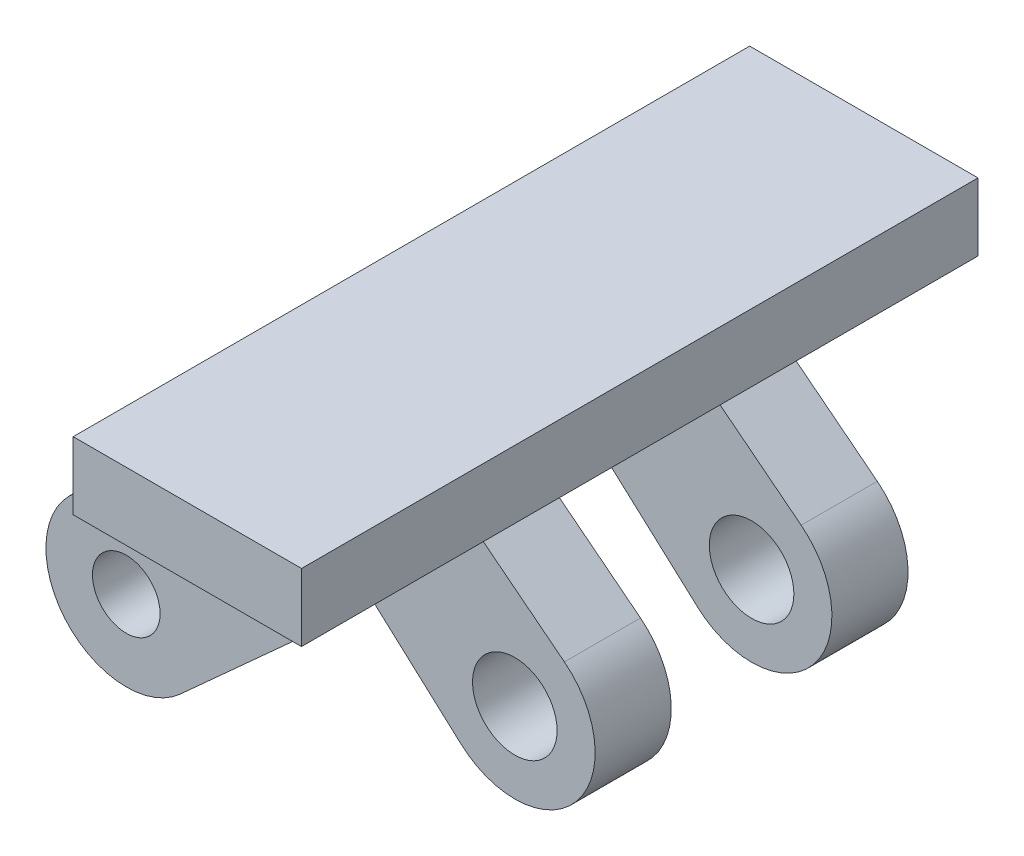
SolidWorks part; units mm, degrees
ref_plane "前视基准面" through (0, 0, 0) normal (0, 0, 1) x (1, 0, 0)
ref_plane "上视基准面" through (0, 0, 0) normal (0, 1, 0) x (1, 0, 0)
ref_plane "右视基准面" through (0, 0, 0) normal (1, 0, 0) x (0, 0, -1)
sketch "草图1" plane through (0, 0, 0) normal (0, 0, 1) x (1, 0, 0)
  line L1 (0, 0) -> (5.4, 0)
  line L2 (0, 0) -> (0, -1.6)
  line L3 (0, -1.6) -> (5.4, -1.6)
  line L4 (5.4, 0) -> (5.4, -1.6)
  dimension "D1" = 1.6
  dimension "D2" = 5.4
extrude "凸台-拉伸1" add sketch "草图1" along normal blind 8 and the other way blind 8
ref_plane "基准面2" through (0, 0, 6) normal (0, 0, 1) x (1, 0, 0)
sketch "草图3" plane through (0, 0, 6) normal (0, 0, 1) x (1, 0, 0)
  line L0 (0, -1.6) -> (-1.9181, -3.1054)
  line L1 (5.4, -1.6) -> (0.5301, -6.0086)
  line L2 (0, -1.6) -> (5.4, -1.6) construction
  line L3 (0, -1.6) -> (5.4, -1.6)
  circle A0 centre (-0.745, -4.6) radius 1.9
  circle A1 centre (-0.745, -4.6) radius 0.8
  point P14 (2.7, -1.6)
  dimension "D1" = 1.6
  dimension "D2" = 3.8
  dimension "D3" = 3
  dimension "D4" = 3.445
extrude "凸台-拉伸2" add sketch "草图3" against normal blind 2 contours A0 A1 | A0 L1 L3 L0 region at (1.9738, -2.7972, 6) region at (0.0625, -2.9397, 6)
ref_plane "基准面1" through (0, 0, 3.7) normal (0, 0, 1) x (1, 0, 0)
sketch "草图5" plane through (0, 0, 3.7) normal (0, 0, 1) x (1, 0, 0)
  line L0 (5.4, -1.6) -> (7.3181, -3.1054)
  line L1 (0, -1.6) -> (4.8699, -6.0086)
  line L2 (6.145, -4.6) -> (-0.745, -4.6) construction
  line L3 (0, -1.6) -> (5.4, -1.6)
  line L4 (0, -1.6) -> (5.4, -1.6) construction
  circle A0 centre (6.145, -4.6) radius 1.9
  circle A1 centre (6.145, -4.6) radius 1
  dimension "D1" = 3.8
  dimension "D2" = 2
  dimension "D3" = 6.89
extrude "凸台-拉伸3" add sketch "草图5" against normal blind 1.8 contours L2 A0 L0 L3 L1 | A1 A0 | A0 L2 L1 region at (3.3991, -2.6973, 3.7) region at (7.8053, -3.7925, 3.7) region at (4.0196, -4.9787, 3.7)
mirror "镜向1" about plane through (0, 0, 0) normal (0, 0, 1) of "凸台-拉伸2", "凸台-拉伸3"
